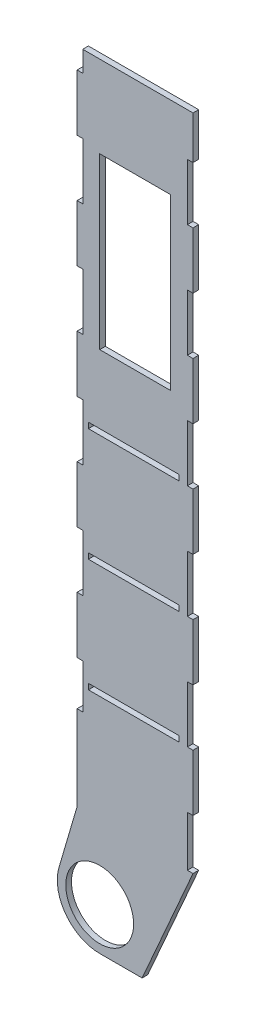
SolidWorks part; units mm, degrees
ref_plane "前视基准面" through (0, 0, 0) normal (0, 0, 1) x (1, 0, 0)
ref_plane "上视基准面" through (0, 0, 0) normal (0, 1, 0) x (1, 0, 0)
ref_plane "右视基准面" through (0, 0, 0) normal (1, 0, 0) x (0, 0, -1)
sketch "草图1" plane through (0, 0, 0) normal (0, 0, 1) x (1, 0, 0)
  line L93 (-8, -48.3425) -> (-6, -48.3425)
  line L100 (-6, -48.3425) -> (-6, -68.3425)
  line L101 (-6, -68.3425) -> (-8, -68.3425)
  line L102 (-8, -68.3425) -> (-8, -88.3425)
  line L103 (-8, -88.3425) -> (-6, -88.3425)
  line L104 (-6, -88.3425) -> (-6, -108.3425)
  line L105 (-6, -108.3425) -> (-8, -108.3425)
  line L106 (-8, -108.3425) -> (-8, -128.3425)
  line L108 (33, -36.2215) -> (31, -36.2215)
  line L109 (31, -36.2215) -> (31, -56.2215)
  line L110 (31, -56.2215) -> (33, -56.2215)
  line L111 (33, -56.2215) -> (33, -76.2215)
  line L112 (33, -76.2215) -> (31, -76.2215)
  line L113 (31, -76.2215) -> (31, -96.2215)
  line L114 (31, -96.2215) -> (33, -96.2215)
  line L117 (33, -96.2215) -> (33, -116.2215)
  line L118 (33, -116.2215) -> (31, -116.2215)
  line L119 (31, -116.2215) -> (31, -136.2215)
  line L120 (31, -136.2215) -> (33, -136.2215)
  line L128 (-4, -56.2215) -> (-4, -54.2215)
  line L129 (-4, -54.2215) -> (28, -54.2215)
  line L130 (28, -54.2215) -> (28, -56.2215)
  line L131 (-4, -56.2215) -> (28, -56.2215)
  line L134 (-4, -94.2215) -> (28, -94.2215)
  line L135 (-4, -96.2215) -> (28, -96.2215)
  line L136 (28, -94.2215) -> (28, -96.2215)
  line L137 (-4, -96.2215) -> (-4, -94.2215)
  line L138 (-4, -134.2215) -> (28, -134.2215)
  line L139 (-4, -136.2215) -> (28, -136.2215)
  line L140 (28, -134.2215) -> (28, -136.2215)
  line L141 (-4, -136.2215) -> (-4, -134.2215)
  line L146 (-8, -174) -> (-14.3926, -195.7746)
  line L148 (0, -215) -> (15, -215)
  line L151 (15, -215) -> (33, -174)
  line L157 (33, 59) -> (33, 49)
  line L158 (33, -36.2215) -> (33, -16.2215)
  line L159 (33, -16.2215) -> (31, -16.2215)
  line L160 (31, -16.2215) -> (31, 3.7785)
  line L161 (31, 3.7785) -> (33, 3.7785)
  line L162 (33, 3.7785) -> (33, 23.7785)
  line L163 (33, 23.7785) -> (31, 23.7785)
  line L164 (31, 23.7785) -> (31, 43.7785)
  line L167 (-8, -48.3425) -> (-8, -28.3425)
  line L168 (-8, -28.3425) -> (-6, -28.3425)
  line L169 (-6, -28.3425) -> (-6, -8.3425)
  line L170 (-6, -8.3425) -> (-8, -8.3425)
  line L171 (-8, -8.3425) -> (-8, 11.6575)
  line L172 (-8, 11.6575) -> (-6, 11.6575)
  line L173 (-6, 11.6575) -> (-6, 31.6575)
  line L174 (-6, 31.6575) -> (-8, 31.6575)
  line L175 (-8, 31.6575) -> (-8, 51.6575)
  line L176 (-8, 51.6575) -> (-6, 51.6575)
  line L177 (-6, 51.6575) -> (-6, 59)
  line L178 (-6, 59) -> (33, 59)
  line L179 (-8, -128.3425) -> (-6, -128.3425)
  line L180 (-6, -128.3425) -> (-6, -144)
  line L181 (-6, -144) -> (-8, -144)
  line L183 (33, -136.2215) -> (33, -156.2215)
  line L184 (33, -156.2215) -> (31, -156.2215)
  line L185 (31, -156.2215) -> (31, -174)
  line L186 (31, -174) -> (33, -174)
  line L187 (-8, -144) -> (-8, -174)
  line L188 (31, 43.7785) -> (33, 43.7785)
  line L189 (33, 43.7785) -> (33, 49)
  line L191 (0, 30) -> (25, 30)
  line L192 (25, 30) -> (25, -30)
  line L194 (0, -30) -> (25, -30)
  line L195 (0, 30) -> (0, -30)
  arc A61 (-14.3926, -195.7746) -> (0, -215) centre (0, -200) ccw
  circle A62 centre (0, -200) radius 12
  dimension "D1" = 3
extrude "凸台-拉伸1" add sketch "草图1" along normal blind 2 contours L146 A61 L148 L151 L186 L185 L184 L183 L120 L119 L118 L117 L114 L113 L112 L111 L110 L109 L108 L158 L159 L160 L161 L162 L163 L164 L188 L189 L157 L178 L177 L176 L175 L174 L173 L172 L171 L170 L169 L168 L167 L93 L100 L101 L102 L103 L104 L105 L106 L179 L180 region at (12.0504, -82.8627, 0)
